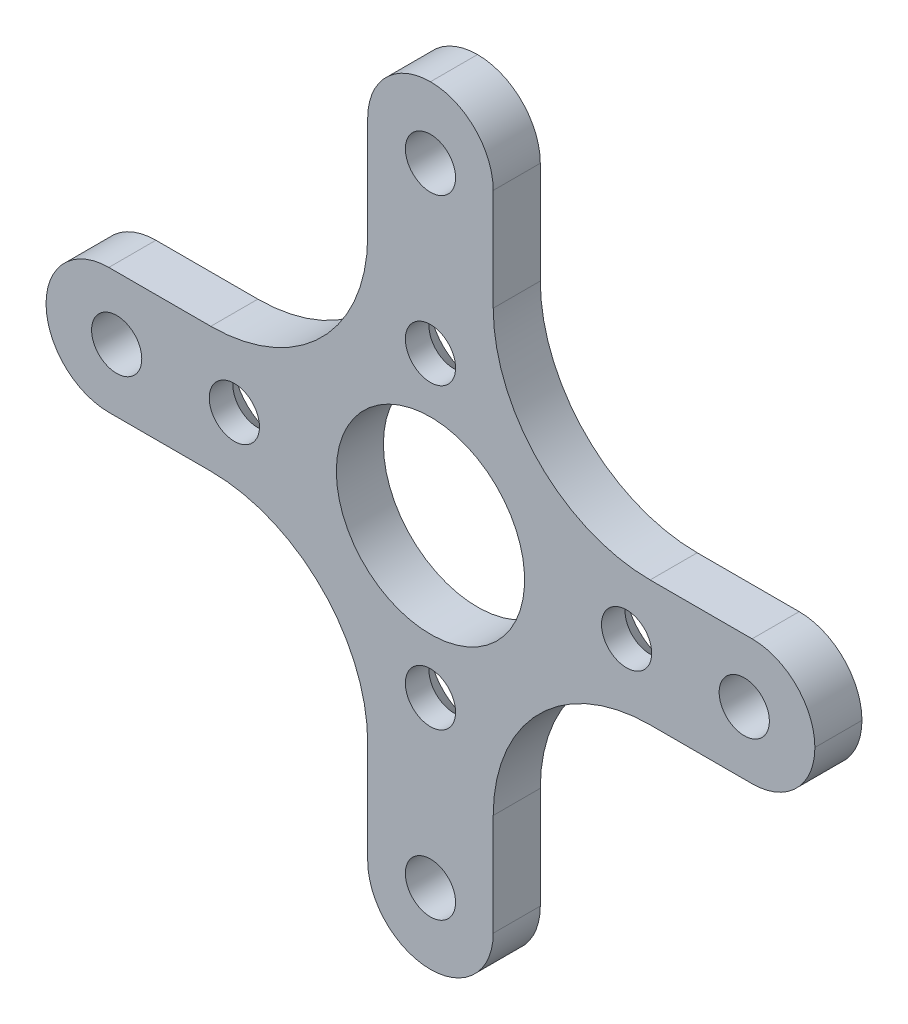
SolidWorks part; units mm, degrees
ref_plane "Plan de face" through (0, 0, 0) normal (0, 0, 1) x (1, 0, 0)
ref_plane "Plan de dessus" through (0, 0, 0) normal (0, 1, 0) x (1, 0, 0)
ref_plane "Plan de droite" through (0, 0, 0) normal (1, 0, 0) x (0, 0, -1)
sketch "Esquisse1" plane through (0, 0, 0) normal (0, 0, 1) x (1, 0, 0)
  line L0 (-11.2842, 20.5) -> (-11.2842, 0)
  line L1 (-11.2842, 0) -> (-31.7842, 0)
  line L2 (-31.7842, 0) -> (-31.7842, -8)
  line L3 (-31.7842, -8) -> (-11.2842, -8)
  line L4 (-11.2842, -8) -> (-11.2842, -28.5)
  line L5 (-11.2842, -28.5) -> (-3.2842, -28.5)
  line L6 (-3.2842, -28.5) -> (-3.2842, -8)
  line L7 (-3.2842, -8) -> (17.2158, -8)
  line L8 (17.2158, -8) -> (17.2158, 0)
  line L9 (17.2158, 0) -> (-3.2842, 0)
  line L10 (-3.2842, 0) -> (-3.2842, 20.5)
  line L11 (-3.2842, 20.5) -> (-11.2842, 20.5)
  point P13 (-7.2842, 20.5)
  point P14 (-7.2842, -28.5)
  dimension "D1" = 49
  dimension "D2" = 8
extrude "Boss.-Extru.1" add sketch "Esquisse1" along normal blind 3
sketch "Esquisse2" plane through (0, 0, 3) normal (0, 0, 1) x (1, 0, 0)
  line L0 (-31.7842, -4) -> (17.2158, -4) construction
  line L1 (-31.7842, 0) -> (-31.7842, -8) construction
  line L2 (17.2158, -8) -> (17.2158, 0) construction
  line L3 (-7.2842, 20.5) -> (-7.2842, -28.5) construction
  line L4 (-3.2842, 20.5) -> (-11.2842, 20.5) construction
  line L5 (-11.2842, -28.5) -> (-3.2842, -28.5) construction
  circle A0 centre (-7.2842, 5.5) radius 1.6
  circle A1 centre (-7.2842, 16) radius 1.6
  circle A2 centre (-7.2842, -13.5) radius 1.6
  circle A3 centre (-7.2842, -24) radius 1.6
  circle A4 centre (-19.7842, -4) radius 1.6
  circle A5 centre (-27.2842, -4) radius 1.6
  circle A6 centre (5.2158, -4) radius 1.6
  circle A7 centre (12.7158, -4) radius 1.6
  point P14 (-7.2842, -4)
  dimension "D1" = 3.2
  dimension "D3" = 3.2
  dimension "D5" = 3.2
  dimension "D7" = 3.2
  dimension "D2" = 9.5
  dimension "D4" = 20
  dimension "D6" = 12.5
  dimension "D8" = 20
extrude "Enlèv. mat.-Extru.1" cut sketch "Esquisse2" against normal up to next contours A5 | A4 | A2 | A0 | A1 | A6 | A7 | A3 region at (-7.2842, 5.5, 3) region at (-7.2842, 16, 3) region at (-7.2842, -13.5, 3) region at (-7.2842, -24, 3) region at (-19.7842, -4, 3) region at (-27.2842, -4, 3) region at (5.2158, -4, 3) region at (12.7158, -4, 3)
fillet "Congé1" radius 10 4 edges at (-3.2842, -8, 1.5) (-11.2842, -8, 1.5) (-11.2842, 0, 1.5) (-3.2842, 0, 1.5)
fillet "Congé2" radius 4 8 edges at (-11.2842, -28.5, 1.5) (-3.2842, -28.5, 1.5) (17.2158, -8, 1.5) (17.2158, 0, 1.5) (-3.2842, 20.5, 1.5) (-11.2842, 20.5, 1.5) (-31.7842, -8, 1.5) (-31.7842, 0, 1.5)
sketch "Esquisse3" plane through (0, 0, 0) normal (0, 0, -1) x (-1, 0, 0)
  line L0 (-17.2158, -4) -> (31.7842, -4) construction
  line L1 (7.2842, 20.5) -> (7.2842, -28.5) construction
  circle A0 centre (7.2842, -4) radius 6
  dimension "D1" = 12
extrude "Enlèv. mat.-Extru.2" cut sketch "Esquisse3" against normal up to next
chamfer "Chanfrein1" distance 1.5 4 edges at (-5.6842, -13.5, 0) (6.8158, -4, 0) (-18.1842, -4, 0) (-5.6842, 5.5, 0)
